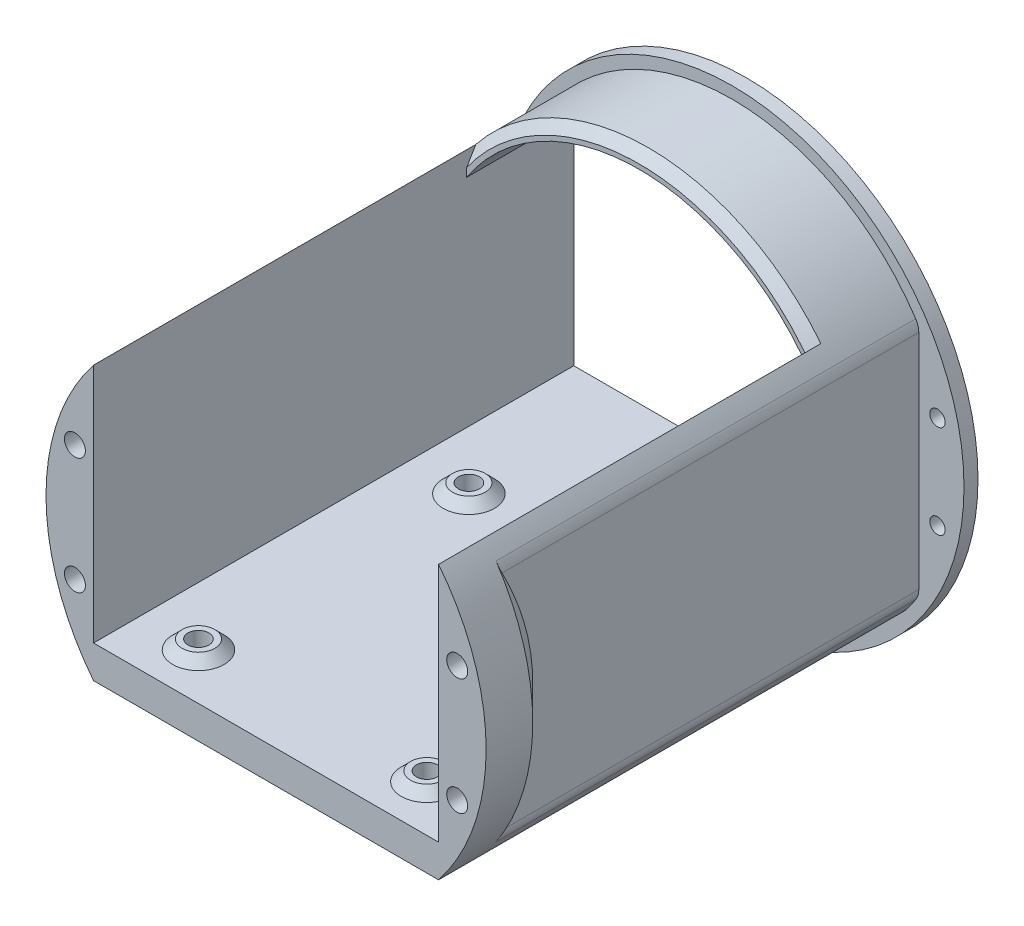
SolidWorks part; units mm, degrees
ref_plane "Front Plane" through (0, 0, 0) normal (0, 0, 1) x (1, 0, 0)
ref_plane "Top Plane" through (0, 0, 0) normal (0, 1, 0) x (1, 0, 0)
ref_plane "Right Plane" through (0, 0, 0) normal (1, 0, 0) x (0, 0, -1)
sketch "Sketch1" plane through (0, 0, 0) normal (0, 0, 1) x (1, 0, 0)
  line L0 (-40, 78.8797) -> (-40, 31.1203) construction
  line L1 (40, 31.1203) -> (40, 78.8797) construction
  line L2 (-40, 78.8797) -> (-40, 31.1203)
  line L3 (40, 31.1203) -> (40, 78.8797)
  circle A1 centre (44, 45) radius 1.65 construction
  circle A2 centre (0, 55) radius 49.7
  circle A3 centre (0, 55) radius 49.7
  circle A4 centre (44, 65) radius 1.65 construction
  circle A5 centre (-44, 65) radius 1.65 construction
  circle A6 centre (-44, 45) radius 1.65 construction
  circle A7 centre (44, 45) radius 1.65
  circle A8 centre (44, 65) radius 1.65
  circle A9 centre (-44, 65) radius 1.65
  circle A10 centre (-44, 45) radius 1.65
  arc A11 (-39.3333, 81.0908) -> (-40, 78.8797) centre (-36, 78.8797) ccw construction
  arc A12 (-40, 31.1203) -> (-39.3333, 28.9092) centre (-36, 31.1203) ccw construction
  arc A13 (-39.3333, 28.9092) -> (39.3333, 28.9092) centre (0, 55) ccw construction
  arc A14 (39.3333, 28.9092) -> (40, 31.1203) centre (36, 31.1203) ccw construction
  arc A15 (40, 78.8797) -> (39.3333, 81.0908) centre (36, 78.8797) ccw construction
  arc A16 (39.3333, 81.0908) -> (-39.3333, 81.0908) centre (0, 55) ccw construction
  arc A17 (-39.3333, 81.0908) -> (-40, 78.8797) centre (-36, 78.8797) ccw
  arc A18 (-40, 31.1203) -> (-39.3333, 28.9092) centre (-36, 31.1203) ccw
  arc A19 (-39.3333, 28.9092) -> (39.3333, 28.9092) centre (0, 55) ccw
  arc A20 (39.3333, 28.9092) -> (40, 31.1203) centre (36, 31.1203) ccw
  arc A21 (40, 78.8797) -> (39.3333, 81.0908) centre (36, 78.8797) ccw
  arc A22 (39.3333, 81.0908) -> (-39.3333, 81.0908) centre (0, 55) ccw
  dimension "D1" = 0.5
extrude "Boss-Extrude1" add sketch "Sketch1" along normal mid plane 3
sketch "Sketch3" plane through (0, 0, 1.5) normal (0, 0, 1) x (1, 0, 0)
  line L0 (-37, 84.306) -> (-37, 32.694)
  line L1 (37, 84.306) -> (37, 32.694)
  line L3 (40, 31.1203) -> (40, 78.8797) construction
  line L4 (-40, 78.8797) -> (-40, 31.1203) construction
  line L5 (40, 31.1203) -> (40, 78.8797)
  line L6 (-40, 78.8797) -> (-40, 31.1203)
  line L8 (-37, 25.694) -> (37, 25.694)
  line L10 (-37, 32.694) -> (37, 32.694)
  circle A0 centre (-44, 65) radius 3.5 construction
  arc A1 (39.3333, 81.0908) -> (-39.3333, 81.0908) centre (0, 55) ccw construction
  circle A2 centre (-44, 45) radius 3.5 construction
  circle A3 centre (44, 45) radius 3.5 construction
  circle A4 centre (44, 65) radius 3.5 construction
  arc A5 (-39.3333, 28.9092) -> (39.3333, 28.9092) centre (0, 55) ccw construction
  arc A6 (40, 78.8797) -> (39.3333, 81.0908) centre (36, 78.8797) ccw construction
  arc A7 (39.3333, 28.9092) -> (40, 31.1203) centre (36, 31.1203) ccw construction
  arc A8 (-40, 31.1203) -> (-39.3333, 28.9092) centre (-36, 31.1203) ccw construction
  arc A9 (-39.3333, 81.0908) -> (-40, 78.8797) centre (-36, 78.8797) ccw construction
  arc A10 (40, 78.8797) -> (39.3333, 81.0908) centre (36, 78.8797) ccw
  arc A11 (39.3333, 28.9092) -> (40, 31.1203) centre (36, 31.1203) ccw
  arc A12 (-39.3333, 28.9092) -> (-37, 25.694) centre (0, 55) ccw
  arc A13 (-40, 31.1203) -> (-39.3333, 28.9092) centre (-36, 31.1203) ccw
  arc A14 (-39.3333, 81.0908) -> (-40, 78.8797) centre (-36, 78.8797) ccw
  arc A15 (39.3333, 81.0908) -> (37, 84.306) centre (0, 55) ccw
  arc A16 (-37, 84.306) -> (-39.3333, 81.0908) centre (0, 55) ccw
  arc A17 (37, 25.694) -> (39.3333, 28.9092) centre (0, 55) ccw
  point P19 (0, 0)
  point P23 (0, 0)
  dimension "D1" = 7
  dimension "D2" = 3
  dimension "D3" = 3
  dimension "D4" = 7
extrude "Boss-Extrude2" add sketch "Sketch3" along normal blind 100 and the other way blind 3
sketch "Sketch4" plane through (0, 32.694, 0) normal (0, 1, 0) x (1, 0, 0)
  line L0 (0, 1.5) -> (0, -91.5) construction
  line L1 (37, 1.5) -> (-37, 1.5) construction
  line L2 (-24.5, -91.5) -> (24.5, -91.5) construction
  line L3 (-24.5, -33.5) -> (24.5, -33.5) construction
  line L4 (37, -101.5) -> (-37, -101.5) construction
  circle A0 centre (-24.5, -91.5) radius 2.25
  circle A1 centre (-24.5, -33.5) radius 2.25
  circle A2 centre (24.5, -33.5) radius 2.25
  circle A3 centre (24.5, -91.5) radius 2.25
  point P7 (0, -91.5)
  point P10 (0, -33.5)
  dimension "D4" = 4.5
  dimension "D1" = 49
  dimension "D2" = 58
  dimension "D3" = 10
extrude "Cut-Extrude1" cut sketch "Sketch4" against normal through all
sketch "Sketch5" plane through (0, 32.694, 0) normal (0, 1, 0) x (1, 0, 0)
  circle A0 centre (-24.5, -33.5) radius 3.5
  circle A1 centre (24.5, -33.5) radius 3.5
  circle A2 centre (24.5, -91.5) radius 3.5
  circle A3 centre (-24.5, -91.5) radius 3.5
  circle A4 centre (24.5, -33.5) radius 2.25 construction
  circle A5 centre (24.5, -91.5) radius 2.25 construction
  circle A6 centre (-24.5, -91.5) radius 2.25 construction
  circle A7 centre (-24.5, -33.5) radius 2.25 construction
  circle A8 centre (24.5, -33.5) radius 2.25
  circle A9 centre (24.5, -91.5) radius 2.25
  circle A10 centre (-24.5, -91.5) radius 2.25
  circle A11 centre (-24.5, -33.5) radius 2.25
  dimension "D1" = 7
extrude "Boss-Extrude3" add sketch "Sketch5" along normal blind 2
chamfer "Chamfer1" distance 2 angle 45 4 edges at (-24.5, 32.694, 95) (24.5, 32.694, 95) (24.5, 32.694, 37) (-24.5, 32.694, 37)
sketch "Sketch6" plane through (0, 0, 101.5) normal (0, 0, 1) x (1, 0, 0)
  line L0 (40, 31.1203) -> (40, 78.8797) construction
  line L1 (-40, 78.8797) -> (-40, 31.1203) construction
  line L2 (40, 31.1203) -> (40, 78.8797)
  line L3 (-40, 78.8797) -> (-40, 31.1203)
  arc A0 (-39.3333, 81.0908) -> (-39.3333, 28.9092) centre (0, 55) ccw
  circle A1 centre (0, 55) radius 49.7 construction
  arc A2 (-37, 25.694) -> (37, 25.694) centre (0, 55) ccw construction
  arc A3 (40, 78.8797) -> (39.3333, 81.0908) centre (36, 78.8797) ccw construction
  arc A4 (39.3333, 28.9092) -> (40, 31.1203) centre (36, 31.1203) ccw construction
  arc A5 (-40, 31.1203) -> (-39.3333, 28.9092) centre (-36, 31.1203) ccw construction
  arc A6 (-39.3333, 81.0908) -> (-40, 78.8797) centre (-36, 78.8797) ccw construction
  arc A7 (40, 78.8797) -> (39.3333, 81.0908) centre (36, 78.8797) ccw
  arc A8 (39.3333, 28.9092) -> (40, 31.1203) centre (36, 31.1203) ccw
  arc A9 (-40, 31.1203) -> (-39.3333, 28.9092) centre (-36, 31.1203) ccw
  arc A10 (-39.3333, 81.0908) -> (-40, 78.8797) centre (-36, 78.8797) ccw
  arc A11 (39.3333, 28.9092) -> (39.3333, 81.0908) centre (0, 55) ccw
extrude "Boss-Extrude4" add sketch "Sketch6" against normal blind 20
chamfer "Chamfer2" distance 10 angle 45 2 edges at (-47.2, 55, 81.5) (47.2, 55, 81.5)
sketch "Sketch7" plane through (0, 0, 101.5) normal (0, 0, 1) x (1, 0, 0)
  line L1 (41, 67.5) -> (-41, 67.5) construction
  line L2 (41, 67.5) -> (41, 42.5) construction
  line L3 (41, 42.5) -> (-41, 42.5) construction
  line L4 (-41, 67.5) -> (-41, 42.5) construction
  line L5 (41, 67.5) -> (-41, 42.5) construction
  line L6 (41, 42.5) -> (-41, 67.5) construction
  circle A0 centre (0, 55) radius 49.7 construction
  circle A1 centre (-41, 67.5) radius 2.25
  circle A2 centre (41, 67.5) radius 2.25
  circle A3 centre (41, 42.5) radius 2.25
  circle A4 centre (-41, 42.5) radius 2.25
  point P0 (0, 55)
  dimension "D3" = 4.5
  dimension "D1" = 82
  dimension "D2" = 25
extrude "Cut-Extrude2" cut sketch "Sketch7" against normal blind 10
sketch "Sketch8" plane through (0, 0, -1.5) normal (0, 0, -1) x (-1, 0, 0)
  line L0 (37, 25.694) -> (-37, 25.694) construction
  line L1 (37, 25.694) -> (-37, 25.694)
  arc A0 (-37, 25.694) -> (37, 25.694) centre (0, 55) ccw construction
  arc A1 (-37, 25.694) -> (37, 25.694) centre (0, 55) ccw
extrude "Boss-Extrude5" add sketch "Sketch8" against normal up to surface (3 mm away) up to face at (-42.35, 65, 1.5)
sketch "Sketch10" plane through (0, 0, 1.5) normal (0, 0, 1) x (1, 0, 0)
  line L0 (-37, 84.306) -> (-37, 79.1793)
  line L1 (37, 84.306) -> (37, 79.1793)
  arc A0 (37, 79.1793) -> (-37, 79.1793) centre (0, 55) ccw
  arc A1 (37, 84.306) -> (-37, 84.306) centre (0, 55) ccw construction
  arc A2 (37, 84.306) -> (-37, 84.306) centre (0, 55) ccw
  dimension "D1" = 3
extrude "Boss-Extrude6" add sketch "Sketch10" along normal blind 20 and the other way blind 3
chamfer "Chamfer3" distance 2 angle 45 1 edges at (0, 102.2, 21.5)
